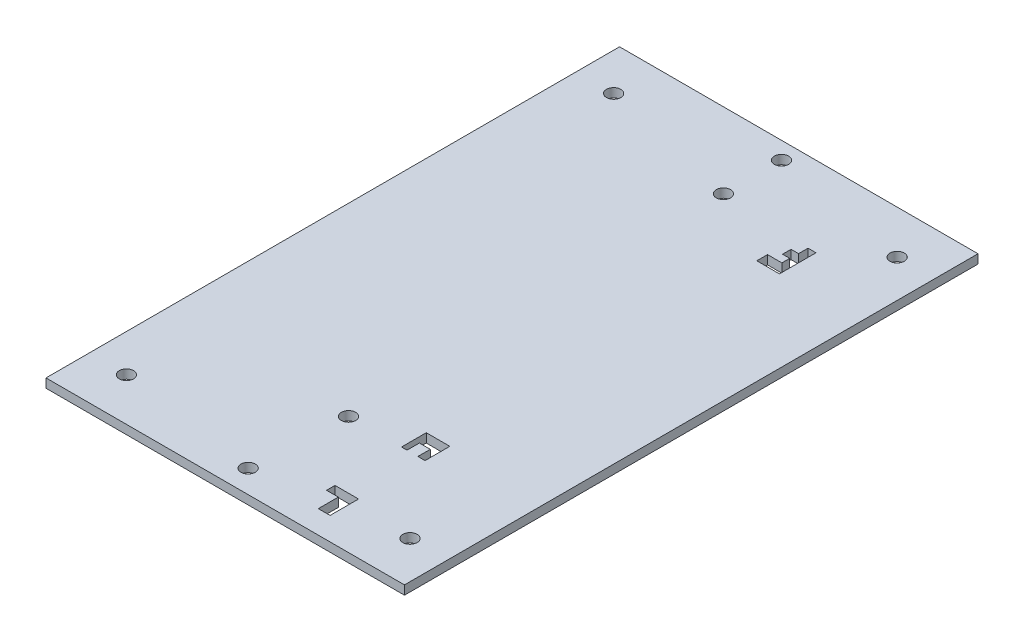
SolidWorks part; units mm, degrees
ref_plane "Front Plane" through (0, 0, 0) normal (0, 0, 1) x (1, 0, 0)
ref_plane "Top Plane" through (0, 0, 0) normal (0, 1, 0) x (1, 0, 0)
ref_plane "Right Plane" through (0, 0, 0) normal (1, 0, 0) x (0, 0, -1)
sketch "Sketch1" plane through (0, 0, 0) normal (0, 1, 0) x (1, 0, 0)
  line L0 (-100.457, -96.0685) -> (100.457, -96.0685) construction
  line L5 (100.457, -96.0685) -> (0, 226.5115) construction
  line L6 (0, 226.5115) -> (-100.457, -96.0685) construction
  line L7 (-100.457, -96.0685) -> (0, 267.6595) construction
  line L8 (0, 267.6595) -> (100.457, -96.0685) construction
  line L9 (-100.457, 249.1485) -> (3.81, -42.9514) construction
  line L10 (-127, 279.8842) -> (127, 279.8842)
  line L11 (-127, 279.8842) -> (-127, -126.5158)
  line L12 (-127, -126.5158) -> (127, -126.5158)
  line L13 (127, 279.8842) -> (127, -126.5158)
  line L14 (3.81, -42.9514) -> (100.457, 249.1485) construction
  line L15 (100.457, 249.1485) -> (-100.457, 249.1485) construction
  line L16 (-100.457, 249.1485) -> (0, -110.2615) construction
  line L17 (0, -110.2615) -> (100.457, 249.1485) construction
  line L18 (69.0129, 197.1736) -> (52.9485, 197.1736)
  line L19 (52.9485, 197.1736) -> (52.9485, 204.7982)
  line L20 (52.9485, 204.7982) -> (63.1353, 204.7982)
  line L21 (63.1353, 204.7982) -> (63.1353, 210.3547)
  line L22 (63.1353, 210.3547) -> (58.0419, 210.3547)
  line L24 (63.3668, 216.3742) -> (63.3668, 223.0882)
  line L25 (63.3668, 223.0882) -> (69.0129, 223.0882)
  line L26 (69.0129, 223.0882) -> (69.0129, 197.1736)
  line L27 (63.3668, 216.3742) -> (58.0419, 216.3742)
  line L28 (58.0419, 216.3742) -> (58.0419, 210.3547)
  line L29 (41.3457, -42.9514) -> (41.3457, -25.4104)
  line L30 (41.3457, -25.4104) -> (58.0419, -25.4104)
  line L31 (58.0419, -25.4104) -> (58.0419, -42.9514)
  line L32 (58.0419, -42.9514) -> (52.9485, -42.9514)
  line L33 (52.9485, -42.9514) -> (52.9485, -34.1809)
  line L34 (52.9485, -34.1809) -> (45.2394, -34.1809)
  line L35 (45.2394, -34.1809) -> (45.2394, -42.9514)
  line L36 (41.3457, -42.9514) -> (45.2394, -42.9514)
  line L37 (58.0419, -110.2615) -> (58.0419, -90.0939)
  line L38 (58.0419, -90.0939) -> (41.3457, -90.0939)
  line L39 (41.3457, -90.0939) -> (41.3457, -96.0685)
  line L40 (41.3457, -96.0685) -> (49.6938, -96.0685)
  line L41 (49.6938, -96.0685) -> (49.6938, -110.2615)
  line L42 (49.6938, -110.2615) -> (58.0419, -110.2615)
  circle A0 centre (-100.457, -96.0685) radius 5.08
  circle A1 centre (100.457, -96.0685) radius 5.08
  circle A2 centre (0, 226.5115) radius 5.08
  circle A3 centre (0, 267.6595) radius 5.08
  circle A4 centre (-100.457, 249.1485) radius 5.08
  circle A5 centre (100.457, 249.1485) radius 5.08
  circle A6 centre (3.81, -42.9514) radius 5.08
  circle A7 centre (0, -110.2615) radius 5.08
  point P6 (0, 279.8842)
  point P13 (0, -96.0685)
  point P20 (0, 249.1485)
  dimension "D1" = 10.16
  dimension "D2" = 10.16
  dimension "D3" = 10.16
  dimension "D9" = 10.16
  dimension "D10" = 310.1516
  dimension "D15" = 254
  dimension "D4" = 337.8601
  dimension "D5" = 337.8601
  dimension "D6" = 200.914
  dimension "D7" = 377.3455
  dimension "D8" = 377.3455
  dimension "D11" = 307.6736
  dimension "D12" = 200.914
  dimension "D13" = 373.1852
  dimension "D14" = 373.1852
  dimension "D16" = 406.4
extrude "Boss-Extrude1" add sketch "Sketch1" along normal blind 6.35
